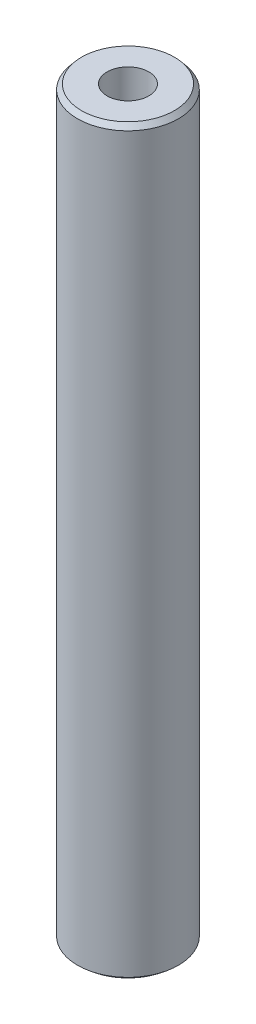
SolidWorks part; units mm, degrees
ref_plane "Front Plane" through (0, 0, 0) normal (0, 0, 1) x (1, 0, 0)
ref_plane "Top Plane" through (0, 0, 0) normal (0, 1, 0) x (1, 0, 0)
ref_plane "Right Plane" through (0, 0, 0) normal (1, 0, 0) x (0, 0, -1)
sketch "Sketch1" plane through (0, 0, 0) normal (0, 1, 0) x (1, 0, 0)
  circle A0 centre (0, 0) radius 32.5
  dimension "SHAFT_OD" = 65
extrude "Boss-Extrude1" add sketch "Sketch1" along normal blind 477.6645
sketch "Sketch2" plane through (0, 0, 0) normal (0, 1, 0) x (1, 0, 0)
  circle A0 centre (0, 0) radius 13.4325
  dimension "BORE_D" = 26.8651
extrude "Cut-Extrude1" cut sketch "Sketch2" along normal through all
chamfer "Chamfer1" distance 3.2037 angle 39.405 2 edges at (0, 477.6645, 32.5) (0, 0, 32.5) first distance on face at (0, 477.6645, 32.5) first distance on face at (0, 0, 13.4325)
